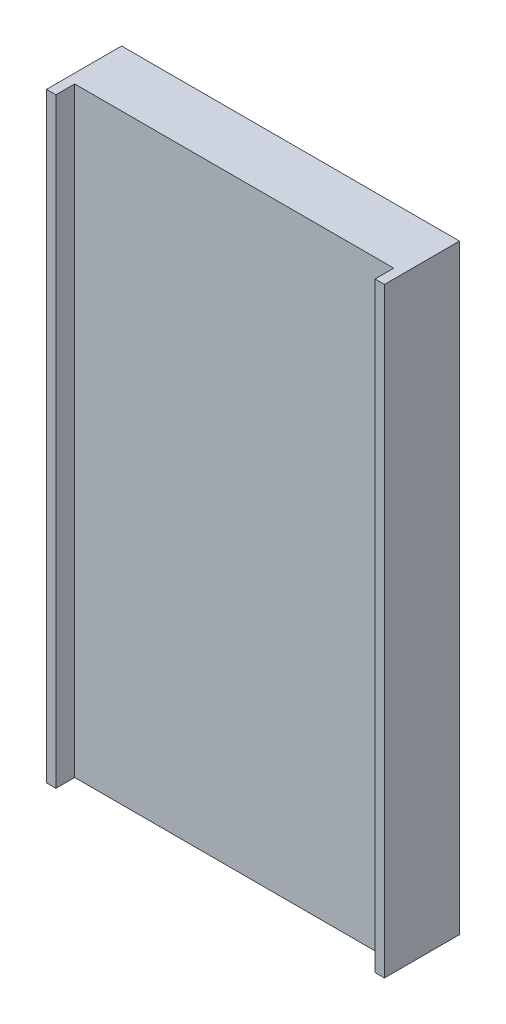
SolidWorks part; units mm, degrees
ref_plane "Front Plane" through (0, 0, 0) normal (0, 0, 1) x (1, 0, 0)
ref_plane "Top Plane" through (0, 0, 0) normal (0, 1, 0) x (1, 0, 0)
ref_plane "Right Plane" through (0, 0, 0) normal (1, 0, 0) x (0, 0, -1)
sketch "Sketch1" plane through (0, 0, 0) normal (0, 0, 1) x (1, 0, 0)
  line L1 (-2.25, 4) -> (2.25, 4)
  line L2 (-2.25, 4) -> (-2.25, -4)
  line L3 (-2.25, -4) -> (2.25, -4)
  line L4 (2.25, 4) -> (2.25, -4)
  line L5 (-2.25, 4) -> (2.25, -4) construction
  line L6 (-2.25, -4) -> (2.25, 4) construction
  line L7 (-2.125, 4) -> (2.125, 4)
  line L8 (-2.125, 4) -> (-2.125, -4)
  line L9 (-2.125, -4) -> (2.125, -4)
  line L10 (2.125, 4) -> (2.125, -4)
  line L11 (-2.125, 4) -> (2.125, -4) construction
  line L12 (-2.125, -4) -> (2.125, 4) construction
  point P0 (0, 0)
  point P6 (0, 0)
  dimension "D1" = 4.5
  dimension "D2" = 8
  dimension "D3" = 4.25
extrude "Boss-Extrude1" add sketch "Sketch1" along normal blind 0.75 contours L10 L1 L8 L3 region at (0, 0, 0)
extrude "Boss-Extrude2" add sketch "Sketch1<3>" along normal blind 1 contours L1 L10 L3 L4 | L8 L1 L2 L3 region at (-2.1875, 0, 0) region at (2.1875, 0, 0)
sketch "Sketch1<3>" plane through (0, 0, 0) normal (0, 0, 1) x (1, 0, 0) same geometry as "Sketch1"
